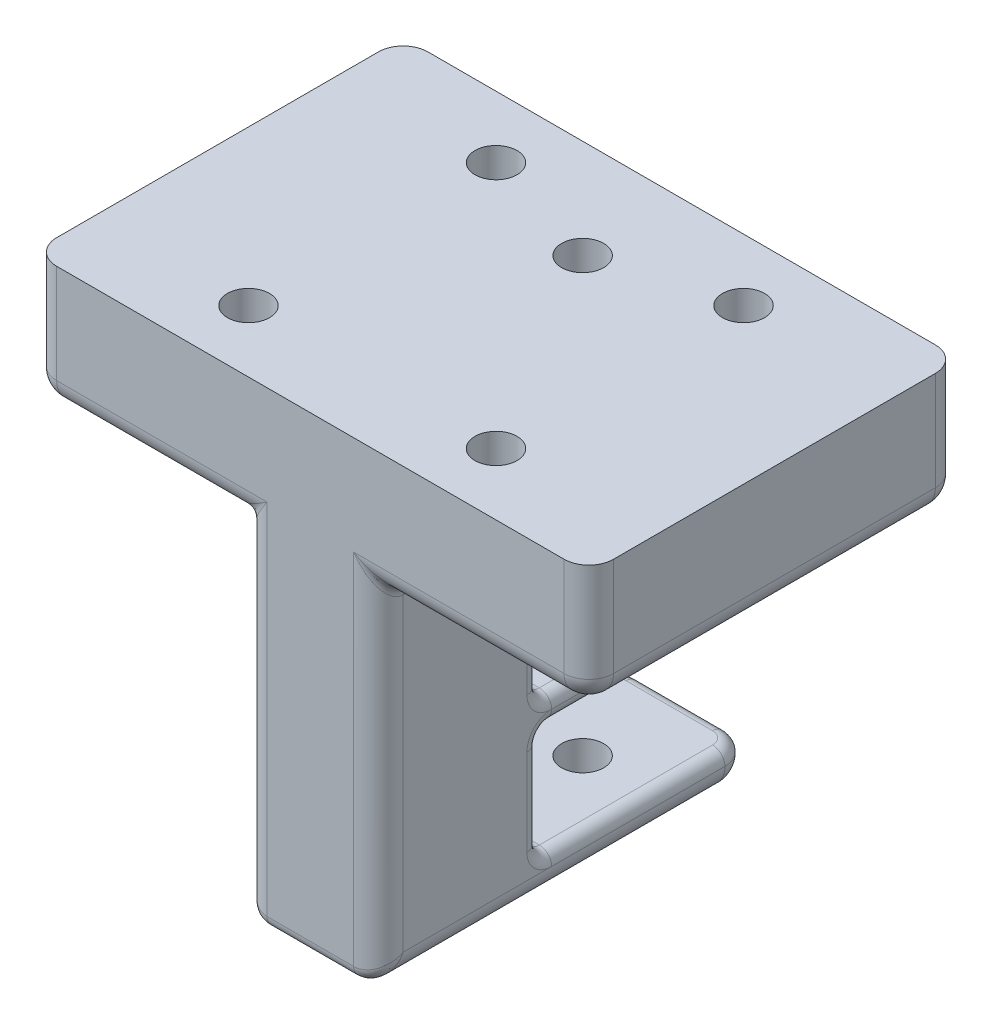
SolidWorks part; units mm, degrees
ref_plane "Front Plane" through (0, 0, 0) normal (0, 0, 1) x (1, 0, 0)
ref_plane "Top Plane" through (0, 0, 0) normal (0, 1, 0) x (1, 0, 0)
ref_plane "Right Plane" through (0, 0, 0) normal (1, 0, 0) x (0, 0, -1)
sketch "Sketch1" plane through (0, 0, 0) normal (0, 1, 0) x (1, 0, 0)
  line L1 (-20.4957, 14.8137) -> (24.5043, 14.8137)
  line L2 (-20.4957, 14.8137) -> (-20.4957, -15.1863)
  line L3 (-20.4957, -15.1863) -> (24.5043, -15.1863)
  line L4 (24.5043, 14.8137) -> (24.5043, -15.1863)
  line L5 (-20.4957, 14.8137) -> (24.5043, -15.1863) construction
  line L6 (-20.4957, -15.1863) -> (24.5043, 14.8137) construction
  line L11 (-7.9957, 9.8137) -> (12.0043, 9.8137) construction
  line L12 (-7.9957, 9.8137) -> (-7.9957, -10.1863) construction
  line L13 (-7.9957, -10.1863) -> (12.0043, -10.1863) construction
  line L14 (12.0043, 9.8137) -> (12.0043, -10.1863) construction
  line L15 (-7.9957, 9.8137) -> (12.0043, -10.1863) construction
  line L16 (-7.9957, -10.1863) -> (12.0043, 9.8137) construction
  circle A0 centre (-7.9957, 9.8137) radius 1.7
  circle A1 centre (12.0043, 9.8137) radius 1.7
  circle A2 centre (12.0043, -10.1863) radius 1.7
  circle A3 centre (-7.9957, -10.1863) radius 1.7
  point P0 (2.0043, -0.1863)
  dimension "D1" = 3.4
  dimension "D2" = 45
  dimension "D3" = 30
  dimension "D4" = 20
  dimension "D5" = 20
extrude "Boss-Extrude1" add sketch "Sketch1" against normal blind 10 contours L4 L1 L2 L3 A3 A2 A1 A0 region at (2.0043, 0, 0.1863)
sketch "Sketch5" plane through (0, -10, 0) normal (0, -1, 0) x (1, 0, 0)
  line L0 (-20.4957, 15.1863) -> (24.5043, 15.1863) construction
  line L1 (-3.4957, 15.1863) -> (7.5043, 15.1863)
  line L2 (-3.4957, 15.1863) -> (-3.4957, -14.8137)
  line L3 (-3.4957, -14.8137) -> (7.5043, -14.8137)
  line L4 (7.5043, 15.1863) -> (7.5043, -14.8137)
  line L5 (-20.4957, -14.8137) -> (24.5043, -14.8137) construction
  line L6 (-20.4957, -14.8137) -> (-20.4957, 15.1863) construction
  line L7 (-20.4957, 15.1863) -> (24.5043, 15.1863) construction
  line L8 (-20.4957, 15.1863) -> (-20.4957, -14.8137) construction
  line L9 (-20.4957, -14.8137) -> (24.5043, -14.8137) construction
  line L10 (24.5043, 15.1863) -> (24.5043, -14.8137) construction
  line L11 (-20.4957, 15.1863) -> (24.5043, -14.8137) construction
  line L12 (-20.4957, -14.8137) -> (24.5043, 15.1863) construction
  line L13 (2.0043, -999.8137) -> (2.0043, 49000.1863) construction
  point P8 (2.0043, 0.1863)
  dimension "D1" = 11
extrude "Boss-Extrude2" add sketch "Sketch5" along normal blind 28
sketch "Sketch7" plane through (0, 0, -14.8137) normal (0, 0, -1) x (-1, 0, 0)
  line L0 (-7.5043, -38) -> (-7.5043, -10) construction
  line L1 (-7.5043, -35) -> (3.4957, -35)
  line L2 (-7.5043, -35) -> (-7.5043, -26)
  line L3 (-7.5043, -26) -> (3.4957, -26)
  line L4 (3.4957, -35) -> (3.4957, -26)
  line L5 (-2.0043, -26) -> (-2.0043, -35) construction
  line L6 (-7.5043, -30.5) -> (3.4957, -30.5) construction
  line L7 (3.4957, -38) -> (3.4957, -10) construction
  line L8 (20.4957, -10) -> (3.4957, -10) construction
  line L9 (-7.5043, -15) -> (3.4957, -15)
  line L10 (-7.5043, -15) -> (-7.5043, -24)
  line L11 (-7.5043, -24) -> (3.4957, -24)
  line L12 (3.4957, -15) -> (3.4957, -24)
  line L13 (-2.0043, -24) -> (-2.0043, -15) construction
  line L14 (-7.5043, -19.5) -> (3.4957, -19.5) construction
  line L15 (3.4957, -38) -> (-7.5043, -38) construction
  point P108 (-2.0043, -19.5)
  point P256 (-2.0043, -30.5)
  dimension "D1" = 5
  dimension "D2" = 3
  dimension "D3" = 9
extrude "Cut-Extrude1" cut sketch "Sketch7" against normal blind 17
sketch "Sketch8" plane through (0, -38, 0) normal (0, -1, 0) x (1, 0, 0)
  line L0 (-3.4957, 15.1863) -> (7.5043, -14.8137) construction
  line L1 (7.5043, 15.1863) -> (-3.4957, -14.8137) construction
  line L2 (2.0043, -995.0009) -> (2.0043, 49004.9991) construction
  line L4 (-3.4957, -14.8137) -> (7.5043, -14.8137) construction
  circle A0 centre (2.0043, -6.8137) radius 1.7
  point P13 (2.0043, 0.1863)
  dimension "D1" = 3.4
  dimension "D2" = 8
extrude "Cut-Extrude2" cut sketch "Sketch8" against normal through all
fillet "Fillet1" radius 2 21 edges at (7.5043, -38, 0.1863) (-3.4957, -38, 0.1863) (-11.9957, -10, 15.1863) (16.0043, -10, 15.1863) (-20.4957, -10, 0.1863) (24.5043, -10, 0.1863) (-11.9957, -10, -14.8137) (16.0043, -10, -14.8137) (7.5043, -12.5, -14.8137) (7.5043, -25, -14.8137) (7.5043, -36.5, -14.8137) (-3.4957, -12.5, -14.8137) (-3.4957, -25, -14.8137) (-3.4957, -36.5, -14.8137) (7.5043, -24, 15.1863) (-3.4957, -24, 15.1863) (2.0043, -38, -14.8137) (-20.4957, -5, -14.8137) (-20.4957, -5, 15.1863) (24.5043, -5, 15.1863) (24.5043, -5, -14.8137)
fillet "Fillet2" radius 1 37 edges at (-2.9099, -9.4142, 14.6006) (-2.9099, -9.4142, -14.2279) (-2.9099, -24, -14.2279) (2.0043, -24, -14.8137) (6.9185, -24, -14.2279) (-2.9099, -26, -14.2279) (2.0043, -26, -14.8137) (6.9185, -26, -14.2279) (-2.9099, -35, -14.2279) (2.0043, -35, -14.8137) (6.9185, -35, -14.2279) (6.9185, -9.4142, -14.2279) (6.9185, -9.4142, 14.6006) (-2.9099, -15, -14.2279) (2.0043, -15, -14.8137) (6.9185, -15, -14.2279) (6.9185, -37.4142, 14.6006) (-2.9099, -37.4142, 14.6006) (-3.4957, -35, -5.3137) (-3.4957, -30.5, 2.1863) (-3.4957, -26, -5.3137) (-3.4957, -24, -5.3137) (-3.4957, -19.5, 2.1863) (-3.4957, -15, -5.3137) (-3.4957, -10, 0.1863) (7.5043, -19.5, 2.1863) (7.5043, -24, -5.3137) (7.5043, -26, -5.3137) (7.5043, -30.5, 2.1863) (7.5043, -35, -5.3137) (7.5043, -10, 0.1863) (7.5043, -15, -5.3137) (2.0043, -38, 15.1863) (2.0043, -15, 2.1863) (2.0043, -24, 2.1863) (2.0043, -26, 2.1863) (2.0043, -35, 2.1863)
